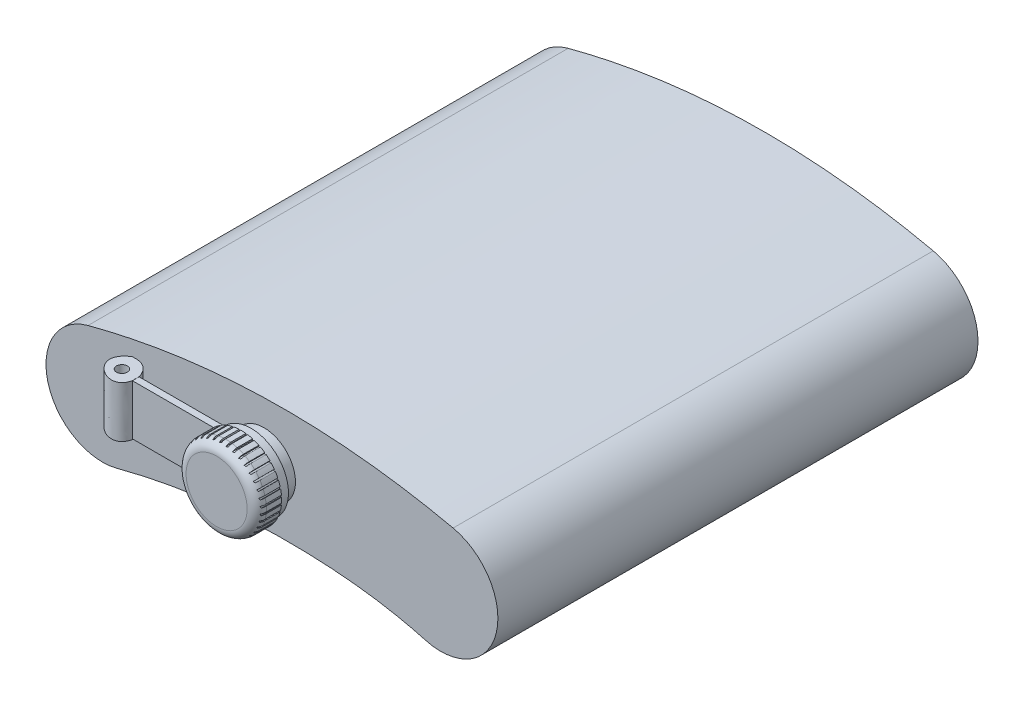
SolidWorks part; units mm, degrees
ref_plane "Front Plane" through (0, 0, 0) normal (0, 0, 1) x (1, 0, 0)
ref_plane "Top Plane" through (0, 0, 0) normal (0, 1, 0) x (1, 0, 0)
ref_plane "Right Plane" through (0, 0, 0) normal (1, 0, 0) x (0, 0, -1)
sketch "Sketch1" plane through (0, 0, 0) normal (0, 0, 1) x (1, 0, 0)
  line L0 (274, 630) -> (1370, 630) construction
  arc A0 (193.4351, 345.2902) -> (231.7057, 200.8231) centre (212.5704, 273.0566) ccw
  arc A6 (639.6364, 208.0275) -> (676.3243, 354.7399) centre (659.9105, 280.9011) ccw
  spline S0 degree 3 poles (676.3243, 354.7399) (610.4182, 369.3903) (449.5376, 389.0952) (288.4205, 370.4527) (193.4351, 345.2902) knots 0 0 0 0 0.409673 1 1 1 1
  spline S1 degree 3 poles (231.7057, 200.8231) (319.0355, 223.9576) (454.7152, 237.6578) (591.1365, 221.5206) (639.6364, 208.0275) knots 0 0 0 0 0.638604 1 1 1 1
extrude "Boss-Extrude1" add sketch "Sketch1" along normal blind 635
sketch "Sketch2" plane through (0, 0, 635) normal (0, 0, 1) x (1, 0, 0)
  circle A0 centre (426.2305, 303.08) radius 41.5651
extrude "Boss-Extrude2" add sketch "Sketch2" along normal blind 17.018
sketch "Sketch3" plane through (0, 0, 652.018) normal (0, 0, 1) x (1, 0, 0)
  circle A0 centre (426.2305, 303.08) radius 49.3387
extrude "Boss-Extrude3" add sketch "Sketch3" along normal blind 12.7
sketch "Sketch4" plane through (0, 0, 664.718) normal (0, 0, 1) x (1, 0, 0)
  circle A0 centre (426.2305, 303.08) radius 53.073
extrude "Boss-Extrude4" add sketch "Sketch4" along normal blind 26.924
sketch "Sketch6" plane through (0, 0, 0) normal (0, 1, 0) x (1, 0, 0)
  line L0 (373.1575, -691.642) -> (479.3035, -691.642) construction
  line L1 (413.8395, -691.642) -> (416.0389, -691.642)
  line L2 (413.8395, -691.642) -> (413.8395, -664.718)
  line L3 (413.8395, -664.718) -> (416.0389, -664.718)
  line L4 (416.0389, -691.642) -> (416.0389, -664.718)
  line L5 (475.5692, -664.718) -> (376.8918, -664.718) construction
extrude "Cut-Extrude1" cut sketch "Sketch6" along normal blind 252.73
pattern_circular "CirPattern1" count 37 over 360 about axis through (426.2305, 303.08, 691.642) along (0, 0, -1) of "Cut-Extrude1"
sketch "Sketch8" plane through (0, 0, 691.642) normal (0, 0, 1) x (1, 0, 0)
  circle A0 centre (426.2305, 303.08) radius 53.073
extrude "Boss-Extrude5" add sketch "Sketch8" along normal blind 6.096
fillet "Fillet1" radius 12.7 1 edges at (479.3035, 303.08, 697.738)
sketch "Sketch9" plane through (0, 0, 0) normal (1, 0, 0) x (0, 0, -1)
  line L1 (-653.4309, 338.7179) -> (-662.3119, 338.7179)
  line L2 (-653.4309, 338.7179) -> (-653.4309, 272.1105)
  line L3 (-653.4309, 272.1105) -> (-662.3119, 272.1105)
  line L4 (-662.3119, 338.7179) -> (-662.3119, 272.1105)
extrude "Boss-Extrude6" add sketch "Sketch9" along normal blind 402.082
sketch "Sketch11" plane through (0, 0, 662.3119) normal (0, 0, 1) x (1, 0, 0)
  line L5 (-25.1392, 435.7368) -> (279.5146, 435.7368)
  line L6 (-25.1392, 435.7368) -> (-25.1392, 212.0773)
  line L7 (-25.1392, 212.0773) -> (279.5146, 212.0773)
  line L8 (279.5146, 435.7368) -> (279.5146, 212.0773)
  spline S0 degree 3 poles (231.7057, 200.8231) (319.0355, 223.9576) (454.7152, 237.6578) (591.1365, 221.5206) (639.6364, 208.0275) knots 0 0 0 0 0.638604 1 1 1 1 construction
extrude "Cut-Extrude2" cut sketch "Sketch11" against normal blind 17.78
sketch "Sketch12" plane through (0, 272.1105, 0) normal (0, -1, 0) x (-1, 0, 0)
  line L0 (-639.6364, -635) -> (-231.7057, -635) construction
  line L5 (-387.8221, -662.3119) -> (-279.5146, -662.3119)
  line L6 (-279.5146, -662.3119) -> (-279.5146, -653.4309)
  line L7 (-279.5146, -653.4309) -> (-387.8221, -653.4309)
  line L8 (-387.8221, -653.4309) -> (-387.8221, -662.3119)
  line L10 (-279.5146, -662.3119) -> (-279.5146, -653.4309)
  spline S0 degree 3 poles (-279.5146, -662.3119) (-272.7901, -695.5788) (-215.6309, -657.7837) (-252.1716, -635) knots 0 0 0 0 1 1 1 1
  spline S1 degree 2 poles (-252.1716, -635) (-273.2481, -633.2247) (-279.5146, -653.4309) knots 0 0 0 1 1 1
  dimension "D1" = 0
extrude "Boss-Extrude7" add sketch "Sketch12" along normal blind 0.762 and the other way blind 66.802
sketch "Sketch13" plane through (0, 271.3485, 0) normal (0, -1, 0) x (-1, 0, 0)
  circle A0 centre (-259.3139, -656.0715) radius 7.2039
extrude "Cut-Extrude3" cut sketch "Sketch13" against normal blind 81.28
